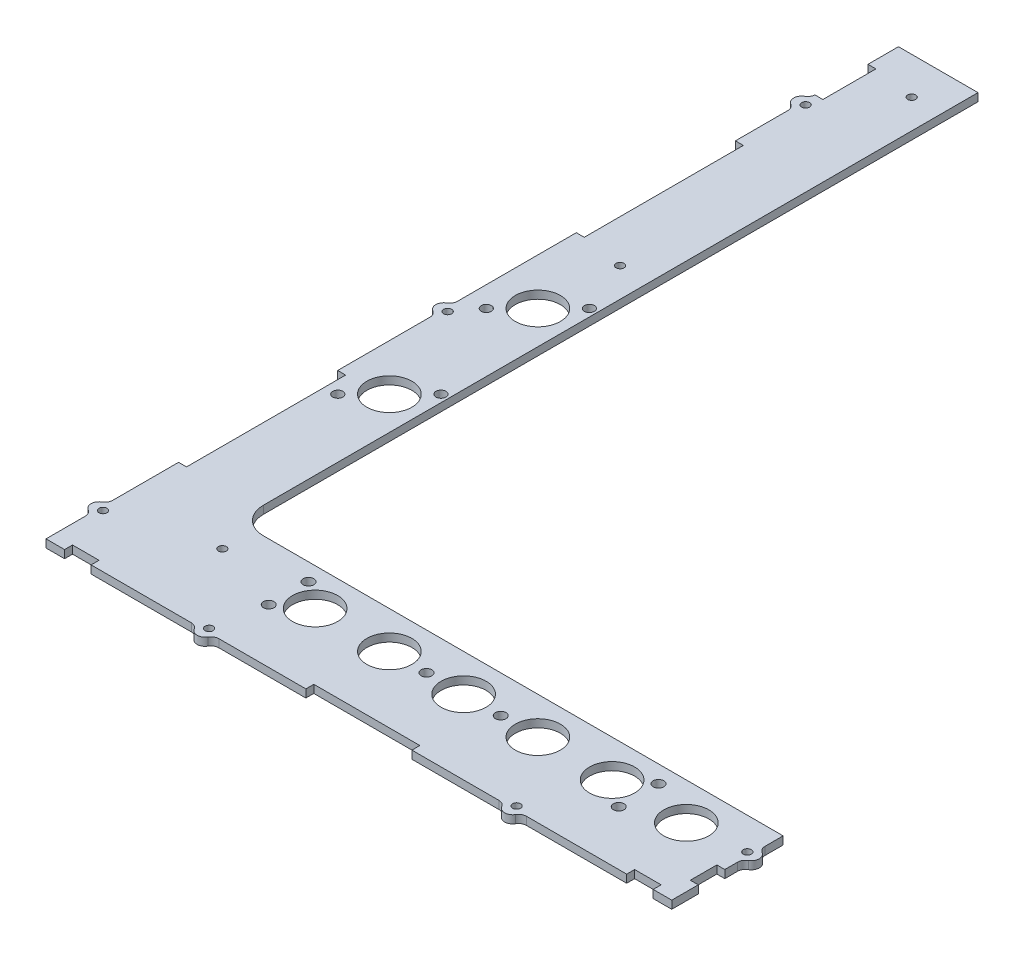
SolidWorks part; units mm, degrees
ref_plane "Спереди" through (0, 0, 0) normal (0, 0, 1) x (1, 0, 0)
ref_plane "Сверху" through (0, 0, 0) normal (0, 1, 0) x (1, 0, 0)
ref_plane "Справа" through (0, 0, 0) normal (1, 0, 0) x (0, 0, -1)
sketch "Эскиз1" plane through (0, 0, 0) normal (0, 1, 0) x (1, 0, 0)
  line L0 (0, 0) -> (0, 321.5)
  line L1 (0, 321.5) -> (30, 321.5)
  line L2 (30, 321.5) -> (30, 42)
  line L3 (30, 42) -> (236, 42)
  line L4 (236, 42) -> (236, 0)
  line L5 (236, 0) -> (0, 0)
  dimension "D1" = 321.5
  dimension "D2" = 236
  dimension "D3" = 42
  dimension "D4" = 30
extrude "Бобышка-Вытянуть1" add sketch "Эскиз1" along normal blind 3
sketch "Эскиз2" plane through (0, 3, 0) normal (0, 1, 0) x (1, 0, 0)
  line L0 (236, 0) -> (236, 42) construction
  line L1 (236, 10) -> (233, 10)
  line L2 (236, 10) -> (236, 20)
  line L3 (236, 20) -> (233, 20)
  line L4 (233, 10) -> (233, 20)
  dimension "D1" = 3
  dimension "D2" = 10
  dimension "D3" = 10
extrude "Вырез-Вытянуть1" cut sketch "Эскиз2" against normal blind 3
sketch "Эскиз4" plane through (236, 0, 0) normal (1, 0, 0) x (0, 0, -1)
  line L0 (20, 3) -> (42, 3) construction
  line L1 (20, 0) -> (42, 0) construction
  line L2 (30, 0) -> (33, 0)
  line L3 (30, 0) -> (30, 3)
  line L4 (30, 3) -> (33, 3)
  line L5 (33, 0) -> (33, 3)
  dimension "D1" = 30
  dimension "D2" = 3
revolve "Повернуть1" add sketch "Эскиз4" angle 360 about L3
fillet "Скругление1" radius 3 2 edges at (236, 1.5, -27) (236, 1.5, -33)
sketch "Эскиз5" plane through (0, 3, 0) normal (0, 1, 0) x (1, 0, 0)
  circle A0 centre (234.5, 30) radius 1.5
  dimension "D1" = 3
  dimension "D2" = 30
  dimension "D3" = 1.5
extrude "Вырез-Вытянуть2" cut sketch "Эскиз5" against normal blind 3
sketch "Эскиз6" plane through (0, 3, 0) normal (0, 1, 0) x (1, 0, 0)
  line L0 (0, 0) -> (236, 0) construction
  line L1 (229, 0) -> (219, 0)
  line L2 (229, 0) -> (229, 3)
  line L3 (229, 3) -> (219, 3)
  line L4 (219, 0) -> (219, 3)
  line L5 (118, 0) -> (118, 12.6976) construction
  line L6 (17, 0) -> (17, 3)
  line L7 (7, 3) -> (17, 3)
  line L8 (7, 0) -> (7, 3)
  line L9 (7, 0) -> (17, 0)
  dimension "D1" = 10
  dimension "D2" = 7
  dimension "D3" = 3
extrude "Вырез-Вытянуть3" cut sketch "Эскиз6" against normal blind 3
sketch "Эскиз7" plane through (0, 3, 0) normal (0, 1, 0) x (1, 0, 0)
  line L0 (17, 0) -> (219, 0) construction
  line L1 (98, 0) -> (138, 0)
  line L2 (98, 0) -> (98, 3)
  line L3 (98, 3) -> (138, 3)
  line L4 (138, 0) -> (138, 3)
  point P6 (118, 0)
  point P7 (118, 0)
  dimension "D1" = 40
  dimension "D2" = 3
extrude "Вырез-Вытянуть4" cut sketch "Эскиз7" against normal blind 3
sketch "Эскиз9" plane through (0, 3, 0) normal (0, 1, 0) x (1, 0, 0)
  line L0 (0, 321.5) -> (0, 0) construction
  line L1 (0, 50) -> (3, 50)
  line L2 (0, 50) -> (0, 110)
  line L3 (0, 110) -> (3, 110)
  line L4 (3, 50) -> (3, 110)
  line L5 (0, 0) -> (7, 0) construction
  line L6 (0, 200) -> (3, 200)
  line L7 (0, 200) -> (0, 260)
  line L8 (0, 260) -> (3, 260)
  line L9 (3, 200) -> (3, 260)
  line L10 (0, 290) -> (3, 290)
  line L11 (0, 290) -> (0, 310)
  line L12 (0, 310) -> (3, 310)
  line L13 (3, 290) -> (3, 310)
  point P16 (3.5, 0)
  dimension "D1" = 3
  dimension "D2" = 3
  dimension "D3" = 3
  dimension "D4" = 20
  dimension "D5" = 60
  dimension "D6" = 60
  dimension "D7" = 50
  dimension "D8" = 200
  dimension "D9" = 290
extrude "Вырез-Вытянуть5" cut sketch "Эскиз9" against normal blind 3
sketch "Эскиз11" plane through (0, 0, 0) normal (0, 0, 1) x (1, 0, 0)
  line L0 (17, 0) -> (98, 0) construction
  line L1 (60, 0) -> (63, 0)
  line L2 (60, 0) -> (60, 3)
  line L3 (60, 3) -> (63, 3)
  line L4 (63, 0) -> (63, 3)
  line L5 (17, 3) -> (98, 3) construction
  dimension "D1" = 3
  dimension "D2" = 60
revolve "Повернуть2" add sketch "Эскиз11" angle 360 about L2
sketch "Эскиз12" plane through (0, 0, 0) normal (0, 0, 1) x (1, 0, 0)
  line L0 (138, 0) -> (219, 0) construction
  line L1 (176, 0) -> (173, 0)
  line L2 (176, 0) -> (176, 3)
  line L3 (176, 3) -> (173, 3)
  line L4 (173, 0) -> (173, 3)
  line L5 (138, 3) -> (219, 3) construction
  dimension "D1" = 3
  dimension "D2" = 60
revolve "Повернуть3" add sketch "Эскиз12" angle 360 about L2
sketch "Эскиз13" plane through (0, 3, 0) normal (0, 1, 0) x (1, 0, 0)
  line L0 (17, 0) -> (57, 0) construction
  circle A0 centre (60, 1.5) radius 1.5
  circle A1 centre (176, 1.5) radius 1.5
  dimension "D1" = 3
  dimension "D2" = 60
  dimension "D3" = 1.5
  dimension "D4" = 60
extrude "Вырез-Вытянуть6" cut sketch "Эскиз13" against normal blind 3
fillet "Скругление2" radius 3 4 edges at (63, 1.5, 0) (57, 1.5, 0) (173, 1.5, 0) (179, 1.5, 0)
sketch "Эскиз14" plane through (0, 0, 0) normal (-1, 0, 0) x (0, 0, 1)
  line L0 (-290, 0) -> (-260, 0) construction
  line L1 (-288, 0) -> (-285, 0)
  line L2 (-288, 0) -> (-288, 3)
  line L3 (-288, 3) -> (-285, 3)
  line L4 (-285, 0) -> (-285, 3)
  line L6 (-290, 3) -> (-260, 3) construction
  dimension "D1" = 3
  dimension "D2" = 285
revolve "Повернуть4" add sketch "Эскиз14" angle 360 about L4
sketch "Эскиз15" plane through (0, 0, 0) normal (-1, 0, 0) x (0, 0, 1)
  line L0 (-200, 0) -> (-110, 0) construction
  line L1 (-153, 0) -> (-150, 0)
  line L2 (-153, 0) -> (-153, 3)
  line L3 (-153, 3) -> (-150, 3)
  line L4 (-150, 0) -> (-150, 3)
  line L5 (-200, 3) -> (-110, 3) construction
  dimension "D1" = 3
  dimension "D2" = 150
revolve "Повернуть5" add sketch "Эскиз15" angle 360 about L4
sketch "Эскиз16" plane through (0, 0, 0) normal (-1, 0, 0) x (0, 0, 1)
  line L0 (-50, 0) -> (0, 0) construction
  line L1 (-23, 0) -> (-20, 0)
  line L2 (-23, 0) -> (-23, 3)
  line L3 (-23, 3) -> (-20, 3)
  line L4 (-20, 0) -> (-20, 3)
  line L5 (-50, 3) -> (0, 3) construction
  dimension "D1" = 3
  dimension "D2" = 20
revolve "Повернуть6" add sketch "Эскиз16" angle 360 about L4
fillet "Скругление3" radius 3 6 edges at (0, 1.5, -288) (0, 1.5, -282) (0, 1.5, -147) (0, 1.5, -153) (0, 1.5, -23) (0, 1.5, -17)
sketch "Эскиз17" plane through (0, 3, 0) normal (0, 1, 0) x (1, 0, 0)
  circle A0 centre (1.5, 20) radius 1.5
  circle A1 centre (1.5, 150) radius 1.5
  circle A2 centre (1.5, 285) radius 1.5
  dimension "D1" = 3
  dimension "D2" = 20
  dimension "D3" = 1.5
  dimension "D4" = 150
  dimension "D5" = 285
extrude "Вырез-Вытянуть7" cut sketch "Эскиз17" against normal blind 3
sketch "Эскиз18" plane through (0, 3, 0) normal (0, 1, 0) x (1, 0, 0)
  line L0 (199.5, 62.1541) -> (199.5, -29.8225) construction
  line L1 (236, 35.1962) -> (236, 42) construction
  line L2 (236, 42) -> (30, 42) construction
  circle A0 centre (213.5, 28) radius 8.5
  dimension "D2" = 17
  dimension "D1" = 36.5
  dimension "D3" = 14
  dimension "D4" = 14
extrude "Вырез-Вытянуть8" cut sketch "Эскиз18" against normal blind 3
pattern_linear "Линейный массив2" count 6 spacing 28 along (-1, 0, 0) of "Вырез-Вытянуть8"
sketch "Эскиз19" plane through (0, 3, 0) normal (0, 1, 0) x (1, 0, 0)
  line L0 (30, 42) -> (30, 321.5) construction
  circle A0 centre (17.5, 112) radius 8.5
  dimension "D1" = 17
  dimension "D2" = 12.5
  dimension "D3" = 112
extrude "Вырез-Вытянуть9" cut sketch "Эскиз19" against normal blind 3
sketch "Эскиз20" plane through (0, 3, 0) normal (0, 1, 0) x (1, 0, 0)
  line L0 (30, 42) -> (30, 321.5) construction
  circle A0 centre (17.5, 168) radius 8.5
  dimension "D1" = 17
  dimension "D2" = 12.5
  dimension "D3" = 168
extrude "Вырез-Вытянуть10" cut sketch "Эскиз20" against normal blind 3
fillet "Скругление4" radius 10 1 edges at (30, 1.5, -42)
sketch "Эскиз21" plane through (0, 3, 0) normal (0, 1, 0) x (1, 0, 0)
  line L0 (101.5, 28) -> (129.5, 28) construction
  circle A0 centre (115.5, 28) radius 2
  circle A1 centre (143.5, 28) radius 2
  circle A2 centre (195.5, 35.5) radius 2
  circle A3 centre (195.5, 20.5) radius 2
  circle A4 centre (63.5, 35.5) radius 2
  circle A5 centre (63.5, 20.5) radius 2
  point P13 (115.5, 28)
  dimension "D1" = 4
  dimension "D6" = 80
  dimension "D2" = 28
  dimension "D3" = 15
  dimension "D4" = 52
  dimension "D5" = 7.5
extrude "Вырез-Вытянуть11" cut sketch "Эскиз21" against normal blind 3
sketch "Эскиз22" plane through (0, 3, 0) normal (0, 1, 0) x (1, 0, 0)
  line L0 (27.2227, 121.7227) -> (17.5, 112) construction
  line L1 (17.5, 112) -> (7.7773, 102.2773) construction
  line L2 (17.5, 112) -> (17.5, 118.1113) construction
  line L3 (27.2227, 177.7227) -> (17.5, 168) construction
  line L4 (17.5, 168) -> (7.7773, 158.2773) construction
  line L5 (17.5, 168) -> (17.5, 202.9694) construction
  circle A0 centre (17.5, 112) radius 13.75 construction
  circle A1 centre (27.2227, 121.7227) radius 1.9
  circle A2 centre (7.7773, 102.2773) radius 1.9
  circle A3 centre (17.5, 168) radius 13.75 construction
  circle A4 centre (27.2227, 177.7227) radius 1.9
  circle A5 centre (7.7773, 158.2773) radius 1.9
  circle A6 centre (17.5, 168) radius 8.5 construction
  point P15 (25.3566, 179.2843)
  dimension "D1" = 27.5
  dimension "D2" = 3.8
  dimension "D4" = 27.5
  dimension "D5" = 3.8
  dimension "D3" = 45
extrude "Вырез-Вытянуть12" cut sketch "Эскиз22" against normal blind 3
sketch "Эскиз23" plane through (0, 3, 0) normal (0, 1, 0) x (1, 0, 0)
  line L0 (0, 200) -> (0, 155.1962) construction
  circle A0 centre (19, 307.5) radius 1.5
  circle A1 centre (19, 197.5) radius 1.5
  dimension "D1" = 3
  dimension "D2" = 197.5
  dimension "D3" = 110
  dimension "D4" = 19
extrude "Вырез-Вытянуть13" cut sketch "Эскиз23" against normal blind 3
sketch "Эскиз24" plane through (0, 3, 0) normal (0, 1, 0) x (1, 0, 0)
  line L0 (17, 0) -> (54.8038, 0) construction
  line L1 (0, 50) -> (0, 25.1962) construction
  circle A0 centre (36.5, 30) radius 1.5
  dimension "D1" = 3
  dimension "D2" = 30
  dimension "D3" = 36.5
extrude "Вырез-Вытянуть14" cut sketch "Эскиз24" against normal blind 3
